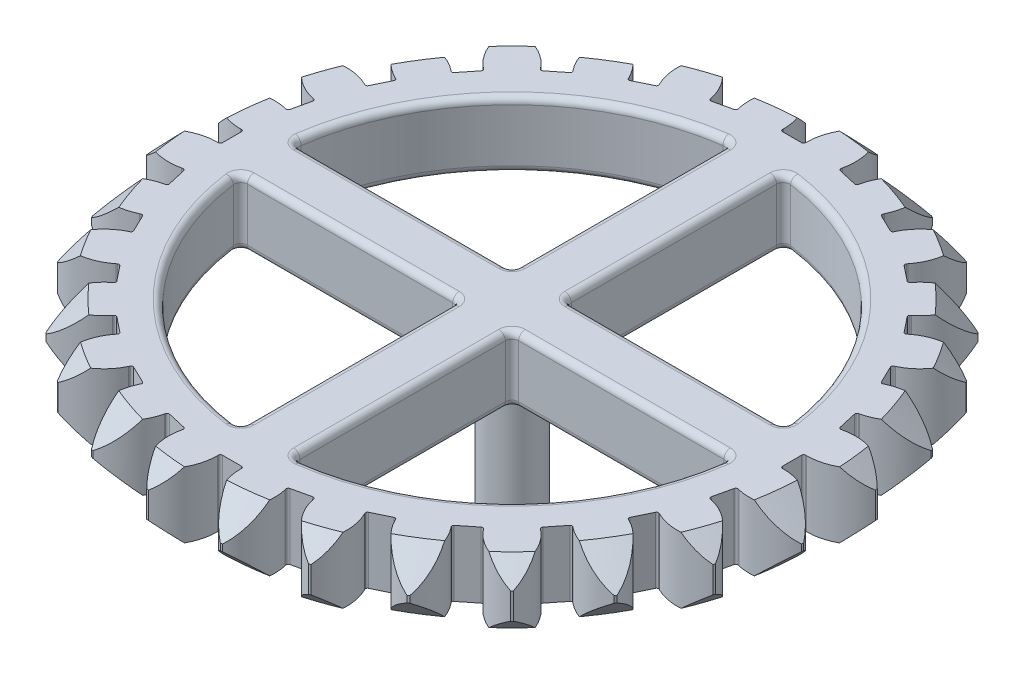
SolidWorks part; units mm, degrees
ref_plane "Front Plane" through (0, 0, 0) normal (0, 0, 1) x (1, 0, 0)
ref_plane "Top Plane" through (0, 0, 0) normal (0, 1, 0) x (1, 0, 0)
ref_plane "Right Plane" through (0, 0, 0) normal (1, 0, 0) x (0, 0, -1)
sketch "Sketch1" plane through (0, 0, 0) normal (0, 1, 0) x (1, 0, 0)
  line L0 (-1.3229, 1.5) -> (1.3229, 1.5)
  circle A0 centre (0, 0) radius 30 construction
  circle A1 centre (0, 0) radius 2
  circle A2 centre (0, 0) radius 4
  dimension "D1" = 60
  dimension "D3" = 4
  dimension "D4" = 2
  dimension "D2" = 0.5
extrude "Boss-Extrude1" add sketch "Sketch1" against normal mid plane 20 contours A2 A1 | L0 A1 region at (0, 0, -1.7023) region at (-3.8869, 0, 0)
sketch "Sketch2" plane through (0, 10, 0) normal (0, 1, 0) x (1, 0, 0)
  line L0 (-1.45, 42.5) -> (1.45, 42.5)
  line L1 (1.75, 42.8) -> (1.75, 42.9644)
  line L2 (0, 0) -> (0, 43) construction
  line L3 (-1.75, 42.8) -> (-1.75, 42.9644)
  line L4 (8.0435, 41.7571) -> (10.8708, 41.1118)
  line L5 (11.23, 41.3375) -> (11.2666, 41.4978)
  line L6 (7.8178, 42.1163) -> (7.8543, 42.2766)
  line L7 (17.1337, 38.9203) -> (19.7465, 37.662)
  line L8 (20.1469, 37.8022) -> (20.2182, 37.9503)
  line L9 (16.9935, 39.3208) -> (17.0648, 39.4689)
  line L10 (25.3647, 34.1319) -> (27.632, 32.3238)
  line L11 (28.0536, 32.3713) -> (28.1561, 32.4998)
  line L12 (25.3172, 34.5535) -> (25.4196, 34.682)
  line L13 (32.3238, 27.632) -> (34.1319, 25.3647)
  line L14 (34.5535, 25.3172) -> (34.682, 25.4196)
  line L15 (32.3713, 28.0536) -> (32.4998, 28.1561)
  line L16 (37.662, 19.7465) -> (38.9203, 17.1337)
  line L17 (39.3208, 16.9935) -> (39.4689, 17.0648)
  line L18 (37.8022, 20.1469) -> (37.9503, 20.2182)
  line L19 (41.1118, 10.8708) -> (41.7571, 8.0435)
  line L20 (42.1163, 7.8178) -> (42.2766, 7.8543)
  line L21 (41.3375, 11.23) -> (41.4978, 11.2666)
  line L22 (42.5, 1.45) -> (42.5, -1.45)
  line L23 (42.8, -1.75) -> (42.9644, -1.75)
  line L24 (42.8, 1.75) -> (42.9644, 1.75)
  line L25 (41.7571, -8.0435) -> (41.1118, -10.8708)
  line L26 (41.3375, -11.23) -> (41.4978, -11.2666)
  line L27 (42.1163, -7.8178) -> (42.2766, -7.8543)
  line L28 (38.9203, -17.1337) -> (37.662, -19.7465)
  line L29 (37.8022, -20.1469) -> (37.9503, -20.2182)
  line L30 (39.3208, -16.9935) -> (39.4689, -17.0648)
  line L31 (34.1319, -25.3647) -> (32.3238, -27.632)
  line L32 (32.3713, -28.0536) -> (32.4998, -28.1561)
  line L33 (34.5535, -25.3172) -> (34.682, -25.4196)
  line L34 (27.632, -32.3238) -> (25.3647, -34.1319)
  line L35 (25.3172, -34.5535) -> (25.4196, -34.682)
  line L36 (28.0536, -32.3713) -> (28.1561, -32.4998)
  line L37 (19.7465, -37.662) -> (17.1337, -38.9203)
  line L38 (16.9935, -39.3208) -> (17.0648, -39.4689)
  line L39 (20.1469, -37.8022) -> (20.2182, -37.9503)
  line L40 (10.8708, -41.1118) -> (8.0435, -41.7571)
  line L41 (7.8178, -42.1163) -> (7.8543, -42.2766)
  line L42 (11.23, -41.3375) -> (11.2666, -41.4978)
  line L43 (1.45, -42.5) -> (-1.45, -42.5)
  line L44 (-1.75, -42.8) -> (-1.75, -42.9644)
  line L45 (1.75, -42.8) -> (1.75, -42.9644)
  line L46 (-8.0435, -41.7571) -> (-10.8708, -41.1118)
  line L47 (-11.23, -41.3375) -> (-11.2666, -41.4978)
  line L48 (-7.8178, -42.1163) -> (-7.8543, -42.2766)
  line L49 (-17.1337, -38.9203) -> (-19.7465, -37.662)
  line L50 (-20.1469, -37.8022) -> (-20.2182, -37.9503)
  line L51 (-16.9935, -39.3208) -> (-17.0648, -39.4689)
  line L52 (-25.3647, -34.1319) -> (-27.632, -32.3238)
  line L53 (-28.0536, -32.3713) -> (-28.1561, -32.4998)
  line L54 (-25.3172, -34.5535) -> (-25.4196, -34.682)
  line L55 (-32.3238, -27.632) -> (-34.1319, -25.3647)
  line L56 (-34.5535, -25.3172) -> (-34.682, -25.4196)
  line L57 (-32.3713, -28.0536) -> (-32.4998, -28.1561)
  line L58 (-37.662, -19.7465) -> (-38.9203, -17.1337)
  line L59 (-39.3208, -16.9935) -> (-39.4689, -17.0648)
  line L60 (-37.8022, -20.1469) -> (-37.9503, -20.2182)
  line L61 (-41.1118, -10.8708) -> (-41.7571, -8.0435)
  line L62 (-42.1163, -7.8178) -> (-42.2766, -7.8543)
  line L63 (-41.3375, -11.23) -> (-41.4978, -11.2666)
  line L64 (-42.5, -1.45) -> (-42.5, 1.45)
  line L65 (-42.8, 1.75) -> (-42.9644, 1.75)
  line L66 (-42.8, -1.75) -> (-42.9644, -1.75)
  line L67 (-41.7571, 8.0435) -> (-41.1118, 10.8708)
  line L68 (-41.3375, 11.23) -> (-41.4978, 11.2666)
  line L69 (-42.1163, 7.8178) -> (-42.2766, 7.8543)
  line L70 (-38.9203, 17.1337) -> (-37.662, 19.7465)
  line L71 (-37.8022, 20.1469) -> (-37.9503, 20.2182)
  line L72 (-39.3208, 16.9935) -> (-39.4689, 17.0648)
  line L73 (-34.1319, 25.3647) -> (-32.3238, 27.632)
  line L74 (-32.3713, 28.0536) -> (-32.4998, 28.1561)
  line L75 (-34.5535, 25.3172) -> (-34.682, 25.4196)
  line L76 (-27.632, 32.3238) -> (-25.3647, 34.1319)
  line L77 (-25.3172, 34.5535) -> (-25.4196, 34.682)
  line L78 (-28.0536, 32.3713) -> (-28.1561, 32.4998)
  line L79 (-19.7465, 37.662) -> (-17.1337, 38.9203)
  line L80 (-16.9935, 39.3208) -> (-17.0648, 39.4689)
  line L81 (-20.1469, 37.8022) -> (-20.2182, 37.9503)
  line L82 (-10.8708, 41.1118) -> (-8.0435, 41.7571)
  line L83 (-7.8178, 42.1163) -> (-7.8543, 42.2766)
  line L84 (-11.23, 41.3375) -> (-11.2666, 41.4978)
  circle A0 centre (0, 0) radius 50
  circle A1 centre (0, 0) radius 43 construction
  arc A2 (1.75, 42.9644) -> (5.4388, 49.7033) centre (9.75, 42.9644) cw
  arc A3 (-1.75, 42.9644) -> (-5.4388, 49.7033) centre (-9.75, 42.9644) ccw
  arc A4 (1.45, 42.5) -> (1.75, 42.8) centre (1.45, 42.8) ccw
  arc A5 (-1.45, 42.5) -> (-1.75, 42.8) centre (-1.45, 42.8) cw
  arc A6 (7.8543, 42.2766) -> (5.7576, 49.6674) centre (0.0549, 44.0567) ccw
  arc A7 (8.0435, 41.7571) -> (7.8178, 42.1163) centre (8.1103, 42.0496) cw
  arc A8 (10.8708, 41.1118) -> (11.23, 41.3375) centre (10.9375, 41.4043) ccw
  arc A9 (11.2666, 41.4978) -> (16.3624, 47.2469) centre (19.066, 39.7176) cw
  arc A10 (17.0648, 39.4689) -> (16.6653, 47.1409) centre (9.8571, 42.9399) ccw
  arc A11 (17.1337, 38.9203) -> (16.9935, 39.3208) centre (17.2638, 39.1906) cw
  arc A12 (19.7465, 37.662) -> (20.1469, 37.8022) centre (19.8766, 37.9323) ccw
  arc A13 (20.2182, 37.9503) -> (26.4656, 42.4213) centre (27.426, 34.4792) cw
  arc A14 (25.4196, 34.682) -> (26.7373, 42.2506) centre (19.165, 39.6699) ccw
  arc A15 (25.3647, 34.1319) -> (25.3172, 34.5535) centre (25.5517, 34.3664) cw
  arc A16 (27.632, 32.3238) -> (28.0536, 32.3713) centre (27.819, 32.5583) ccw
  arc A17 (28.1561, 32.4998) -> (35.2417, 35.4686) centre (34.4107, 27.5119) cw
  arc A18 (32.4998, 28.1561) -> (35.4686, 35.2417) centre (27.5119, 34.4107) ccw
  arc A19 (32.3238, 27.632) -> (32.3713, 28.0536) centre (32.5583, 27.819) cw
  arc A20 (34.1319, 25.3647) -> (34.5535, 25.3172) centre (34.3664, 25.5517) ccw
  arc A21 (34.682, 25.4196) -> (42.2506, 26.7373) centre (39.6699, 19.165) cw
  arc A22 (37.9503, 20.2182) -> (42.4213, 26.4656) centre (34.4792, 27.426) ccw
  arc A23 (37.662, 19.7465) -> (37.8022, 20.1469) centre (37.9323, 19.8766) cw
  arc A24 (38.9203, 17.1337) -> (39.3208, 16.9935) centre (39.1906, 17.2638) ccw
  arc A25 (39.4689, 17.0648) -> (47.1409, 16.6653) centre (42.9399, 9.8571) cw
  arc A26 (41.4978, 11.2666) -> (47.2469, 16.3624) centre (39.7176, 19.066) ccw
  arc A27 (41.1118, 10.8708) -> (41.3375, 11.23) centre (41.4043, 10.9375) cw
  arc A28 (41.7571, 8.0435) -> (42.1163, 7.8178) centre (42.0496, 8.1103) ccw
  arc A29 (42.2766, 7.8543) -> (49.6674, 5.7576) centre (44.0567, 0.0549) cw
  arc A30 (42.9644, 1.75) -> (49.7033, 5.4388) centre (42.9644, 9.75) ccw
  arc A31 (42.5, 1.45) -> (42.8, 1.75) centre (42.8, 1.45) cw
  arc A32 (42.5, -1.45) -> (42.8, -1.75) centre (42.8, -1.45) ccw
  arc A33 (42.9644, -1.75) -> (49.7033, -5.4388) centre (42.9644, -9.75) cw
  arc A34 (42.2766, -7.8543) -> (49.6674, -5.7576) centre (44.0567, -0.0549) ccw
  arc A35 (41.7571, -8.0435) -> (42.1163, -7.8178) centre (42.0496, -8.1103) cw
  arc A36 (41.1118, -10.8708) -> (41.3375, -11.23) centre (41.4043, -10.9375) ccw
  arc A37 (41.4978, -11.2666) -> (47.2469, -16.3624) centre (39.7176, -19.066) cw
  arc A38 (39.4689, -17.0648) -> (47.1409, -16.6653) centre (42.9399, -9.8571) ccw
  arc A39 (38.9203, -17.1337) -> (39.3208, -16.9935) centre (39.1906, -17.2638) cw
  arc A40 (37.662, -19.7465) -> (37.8022, -20.1469) centre (37.9323, -19.8766) ccw
  arc A41 (37.9503, -20.2182) -> (42.4213, -26.4656) centre (34.4792, -27.426) cw
  arc A42 (34.682, -25.4196) -> (42.2506, -26.7373) centre (39.6699, -19.165) ccw
  arc A43 (34.1319, -25.3647) -> (34.5535, -25.3172) centre (34.3664, -25.5517) cw
  arc A44 (32.3238, -27.632) -> (32.3713, -28.0536) centre (32.5583, -27.819) ccw
  arc A45 (32.4998, -28.1561) -> (35.4686, -35.2417) centre (27.5119, -34.4107) cw
  arc A46 (28.1561, -32.4998) -> (35.2417, -35.4686) centre (34.4107, -27.5119) ccw
  arc A47 (27.632, -32.3238) -> (28.0536, -32.3713) centre (27.819, -32.5583) cw
  arc A48 (25.3647, -34.1319) -> (25.3172, -34.5535) centre (25.5517, -34.3664) ccw
  arc A49 (25.4196, -34.682) -> (26.7373, -42.2506) centre (19.165, -39.6699) cw
  arc A50 (20.2182, -37.9503) -> (26.4656, -42.4213) centre (27.426, -34.4792) ccw
  arc A51 (19.7465, -37.662) -> (20.1469, -37.8022) centre (19.8766, -37.9323) cw
  arc A52 (17.1337, -38.9203) -> (16.9935, -39.3208) centre (17.2638, -39.1906) ccw
  arc A53 (17.0648, -39.4689) -> (16.6653, -47.1409) centre (9.8571, -42.9399) cw
  arc A54 (11.2666, -41.4978) -> (16.3624, -47.2469) centre (19.066, -39.7176) ccw
  arc A55 (10.8708, -41.1118) -> (11.23, -41.3375) centre (10.9375, -41.4043) cw
  arc A56 (8.0435, -41.7571) -> (7.8178, -42.1163) centre (8.1103, -42.0496) ccw
  arc A57 (7.8543, -42.2766) -> (5.7576, -49.6674) centre (0.0549, -44.0567) cw
  arc A58 (1.75, -42.9644) -> (5.4388, -49.7033) centre (9.75, -42.9644) ccw
  arc A59 (1.45, -42.5) -> (1.75, -42.8) centre (1.45, -42.8) cw
  arc A60 (-1.45, -42.5) -> (-1.75, -42.8) centre (-1.45, -42.8) ccw
  arc A61 (-1.75, -42.9644) -> (-5.4388, -49.7033) centre (-9.75, -42.9644) cw
  arc A62 (-7.8543, -42.2766) -> (-5.7576, -49.6674) centre (-0.0549, -44.0567) ccw
  arc A63 (-8.0435, -41.7571) -> (-7.8178, -42.1163) centre (-8.1103, -42.0496) cw
  arc A64 (-10.8708, -41.1118) -> (-11.23, -41.3375) centre (-10.9375, -41.4043) ccw
  arc A65 (-11.2666, -41.4978) -> (-16.3624, -47.2469) centre (-19.066, -39.7176) cw
  arc A66 (-17.0648, -39.4689) -> (-16.6653, -47.1409) centre (-9.8571, -42.9399) ccw
  arc A67 (-17.1337, -38.9203) -> (-16.9935, -39.3208) centre (-17.2638, -39.1906) cw
  arc A68 (-19.7465, -37.662) -> (-20.1469, -37.8022) centre (-19.8766, -37.9323) ccw
  arc A69 (-20.2182, -37.9503) -> (-26.4656, -42.4213) centre (-27.426, -34.4792) cw
  arc A70 (-25.4196, -34.682) -> (-26.7373, -42.2506) centre (-19.165, -39.6699) ccw
  arc A71 (-25.3647, -34.1319) -> (-25.3172, -34.5535) centre (-25.5517, -34.3664) cw
  arc A72 (-27.632, -32.3238) -> (-28.0536, -32.3713) centre (-27.819, -32.5583) ccw
  arc A73 (-28.1561, -32.4998) -> (-35.2417, -35.4686) centre (-34.4107, -27.5119) cw
  arc A74 (-32.4998, -28.1561) -> (-35.4686, -35.2417) centre (-27.5119, -34.4107) ccw
  arc A75 (-32.3238, -27.632) -> (-32.3713, -28.0536) centre (-32.5583, -27.819) cw
  arc A76 (-34.1319, -25.3647) -> (-34.5535, -25.3172) centre (-34.3664, -25.5517) ccw
  arc A77 (-34.682, -25.4196) -> (-42.2506, -26.7373) centre (-39.6699, -19.165) cw
  arc A78 (-37.9503, -20.2182) -> (-42.4213, -26.4656) centre (-34.4792, -27.426) ccw
  arc A79 (-37.662, -19.7465) -> (-37.8022, -20.1469) centre (-37.9323, -19.8766) cw
  arc A80 (-38.9203, -17.1337) -> (-39.3208, -16.9935) centre (-39.1906, -17.2638) ccw
  arc A81 (-39.4689, -17.0648) -> (-47.1409, -16.6653) centre (-42.9399, -9.8571) cw
  arc A82 (-41.4978, -11.2666) -> (-47.2469, -16.3624) centre (-39.7176, -19.066) ccw
  arc A83 (-41.1118, -10.8708) -> (-41.3375, -11.23) centre (-41.4043, -10.9375) cw
  arc A84 (-41.7571, -8.0435) -> (-42.1163, -7.8178) centre (-42.0496, -8.1103) ccw
  arc A85 (-42.2766, -7.8543) -> (-49.6674, -5.7576) centre (-44.0567, -0.0549) cw
  arc A86 (-42.9644, -1.75) -> (-49.7033, -5.4388) centre (-42.9644, -9.75) ccw
  arc A87 (-42.5, -1.45) -> (-42.8, -1.75) centre (-42.8, -1.45) cw
  arc A88 (-42.5, 1.45) -> (-42.8, 1.75) centre (-42.8, 1.45) ccw
  arc A89 (-42.9644, 1.75) -> (-49.7033, 5.4388) centre (-42.9644, 9.75) cw
  arc A90 (-42.2766, 7.8543) -> (-49.6674, 5.7576) centre (-44.0567, 0.0549) ccw
  arc A91 (-41.7571, 8.0435) -> (-42.1163, 7.8178) centre (-42.0496, 8.1103) cw
  arc A92 (-41.1118, 10.8708) -> (-41.3375, 11.23) centre (-41.4043, 10.9375) ccw
  arc A93 (-41.4978, 11.2666) -> (-47.2469, 16.3624) centre (-39.7176, 19.066) cw
  arc A94 (-39.4689, 17.0648) -> (-47.1409, 16.6653) centre (-42.9399, 9.8571) ccw
  arc A95 (-38.9203, 17.1337) -> (-39.3208, 16.9935) centre (-39.1906, 17.2638) cw
  arc A96 (-37.662, 19.7465) -> (-37.8022, 20.1469) centre (-37.9323, 19.8766) ccw
  arc A97 (-37.9503, 20.2182) -> (-42.4213, 26.4656) centre (-34.4792, 27.426) cw
  arc A98 (-34.682, 25.4196) -> (-42.2506, 26.7373) centre (-39.6699, 19.165) ccw
  arc A99 (-34.1319, 25.3647) -> (-34.5535, 25.3172) centre (-34.3664, 25.5517) cw
  arc A100 (-32.3238, 27.632) -> (-32.3713, 28.0536) centre (-32.5583, 27.819) ccw
  arc A101 (-32.4998, 28.1561) -> (-35.4686, 35.2417) centre (-27.5119, 34.4107) cw
  arc A102 (-28.1561, 32.4998) -> (-35.2417, 35.4686) centre (-34.4107, 27.5119) ccw
  arc A103 (-27.632, 32.3238) -> (-28.0536, 32.3713) centre (-27.819, 32.5583) cw
  arc A104 (-25.3647, 34.1319) -> (-25.3172, 34.5535) centre (-25.5517, 34.3664) ccw
  arc A105 (-25.4196, 34.682) -> (-26.7373, 42.2506) centre (-19.165, 39.6699) cw
  arc A106 (-20.2182, 37.9503) -> (-26.4656, 42.4213) centre (-27.426, 34.4792) ccw
  arc A107 (-19.7465, 37.662) -> (-20.1469, 37.8022) centre (-19.8766, 37.9323) cw
  arc A108 (-17.1337, 38.9203) -> (-16.9935, 39.3208) centre (-17.2638, 39.1906) ccw
  arc A109 (-17.0648, 39.4689) -> (-16.6653, 47.1409) centre (-9.8571, 42.9399) cw
  arc A110 (-11.2666, 41.4978) -> (-16.3624, 47.2469) centre (-19.066, 39.7176) ccw
  arc A111 (-10.8708, 41.1118) -> (-11.23, 41.3375) centre (-10.9375, 41.4043) cw
  arc A112 (-8.0435, 41.7571) -> (-7.8178, 42.1163) centre (-8.1103, 42.0496) ccw
  arc A113 (-7.8543, 42.2766) -> (-5.7576, 49.6674) centre (-0.0549, 44.0567) cw
  point P6 (0, 42.5)
  point P20 (1.75, 42.5)
  point P23 (-1.75, 42.5)
  point P202 (0, 0)
  arc M1 (1.3229, 1.5) -> (-1.3229, 1.5) centre (0, 0) cw
  line M2 (-1.3229, 1.5) -> (1.3229, 1.5)
  circle M3 centre (0, 0) radius 4
  dimension "D1" = 100
  dimension "D2" = 7
  dimension "D4" = 8
  dimension "D6" = 0.3
  dimension "D3" = 0.5
  dimension "D5" = 3.5
  dimension "D7" = 28
extrude "Boss-Extrude2" add sketch "Sketch2" along normal blind 10 contours A65 L47 A64 L46 A63 L48 A62 A0 A61 L44 A60 L43 A59 L45 A58 A57 L41 A56 L40 A55 L42 A54 A53 L38 A52 L37 A51 L39 A50 A49 L35 A48 L34 A47 L36 A46 A45 L32 A44 L31 A43 L33 A42 A41 L29 A40 | M3 M2 M1 | M1 M2 region at (0, 10, -41.0942) region at (0, 10, 0.1324) region at (-3.8869, 10, 0)
sketch "Sketch3" plane through (0, 20, 0) normal (0, 1, 0) x (1, 0, 0)
  line L0 (-1.45, 42.5) -> (1.45, 42.5) construction
  line L1 (-4, 3) -> (-4, 37.2861)
  line L2 (4, 3) -> (4, 37.2861)
  line L3 (-4, 3) -> (4, 3) construction
  line L4 (3, 4) -> (37.2861, 4)
  line L5 (3, -4) -> (37.2861, -4)
  line L6 (4, -3) -> (4, -37.2861)
  line L7 (-4, -3) -> (-4, -37.2861)
  line L8 (-3, -4) -> (-37.2861, -4)
  line L9 (-3, 4) -> (-37.2861, 4)
  circle A0 centre (0, 0) radius 42.5
  circle A1 centre (0, 0) radius 37.5
  circle A2 centre (0, 0) radius 5
  point P12 (0, 3)
  point P35 (0, 0)
  dimension "D2" = 10
  dimension "D3" = 8
  dimension "D1" = 5
  dimension "D4" = 4
extrude "Cut-Extrude2" cut sketch "Sketch3" against normal up to next contours A2 L4 A1 L2 | A2 L1 A1 L9 | A2 L6 A1 L5 | A2 L8 A1 L7 region at (-17.6718, 20, -17.6718) region at (-17.6718, 20, 17.6718) region at (17.6718, 20, -17.6718) region at (17.6718, 20, 17.6718)
fillet "Fillet1" radius 1 36 edges at (4, 10, -20.643) (4, 20, -20.643) (4, 15, -37.2861) (26.5165, 20, -26.5165) (26.5165, 10, -26.5165) (37.2861, 15, -4) (20.643, 20, -4) (20.643, 10, -4) (-4, 10, 20.643) (-4, 20, 20.643) (-4, 15, 37.2861) (-26.5165, 20, 26.5165) (-26.5165, 10, 26.5165) (-37.2861, 15, 4) (-20.643, 20, 4) (-20.643, 10, 4) (20.643, 10, 4) (20.643, 20, 4) (37.2861, 15, 4) (26.5165, 20, 26.5165) (26.5165, 10, 26.5165) (4, 15, 37.2861) (4, 20, 20.643) (4, 10, 20.643) (-20.643, 10, -4) (-20.643, 20, -4) (-37.2861, 15, -4) (-26.5165, 20, -26.5165) (-26.5165, 10, -26.5165) (-4, 15, -37.2861) (-4, 20, -20.643) (-4, 10, -20.643) (4, 15, -4) (-4, 15, 4) (4, 15, 4) (-4, 15, -4)
sketch "Sketch4" plane through (0, 10, 0) normal (0, -1, 0) x (1, 0, 0)
  circle A0 centre (0, 0) radius 2
  arc A1 (1.3229, -1.5) -> (-1.3229, -1.5) centre (0, 0) ccw construction
extrude "Boss-Extrude3" add sketch "Sketch4" along normal blind 10
sketch "Sketch5" plane through (0, 0, 0) normal (0, 0, 1) x (1, 0, 0)
  line L0 (47, 20) -> (50, 17)
  line L1 (50, 17) -> (50, 20)
  line L2 (50, 20) -> (47, 20)
  line L3 (38.1559, 20) -> (36.1559, 20) construction
  line L4 (0, 0) -> (0, 20) construction
  point P5 (0, 0)
  dimension "D1" = 50
  dimension "D2" = 45
  dimension "D3" = 3
revolve "Cut-Revolve1" cut sketch "Sketch5" angle 360 about L4
sketch "Sketch6" plane through (0, 0, 0) normal (1, 0, 0) x (0, 0, -1)
  line L0 (45.5, 20) -> (50, 20)
  line L1 (50, 20) -> (50, 15.5)
  line L2 (50, 15.5) -> (45.5, 20)
  line L3 (5.274, 20) -> (3, 20) construction
  line L4 (0, 0) -> (0, 20) construction
  point P9 (0, 0)
  dimension "D1" = 50
  dimension "D2" = 45
  dimension "D3" = 4.5
revolve "Cut-Revolve2" cut sketch "Sketch6" angle 15 about L4
pattern_circular "CirPattern1" count 14 over 360 about axis through (0, -10, 0) along (0, 1, 0) of "Cut-Revolve2"
ref_plane "Plane2" through (0, 15, 0) normal (0, -1, 0) x (-1, 0, 0)
mirror "Mirror1" about plane through (0, 15, 0) normal (0, -1, 0) of "CirPattern1", "Cut-Revolve1", "Cut-Revolve2"
